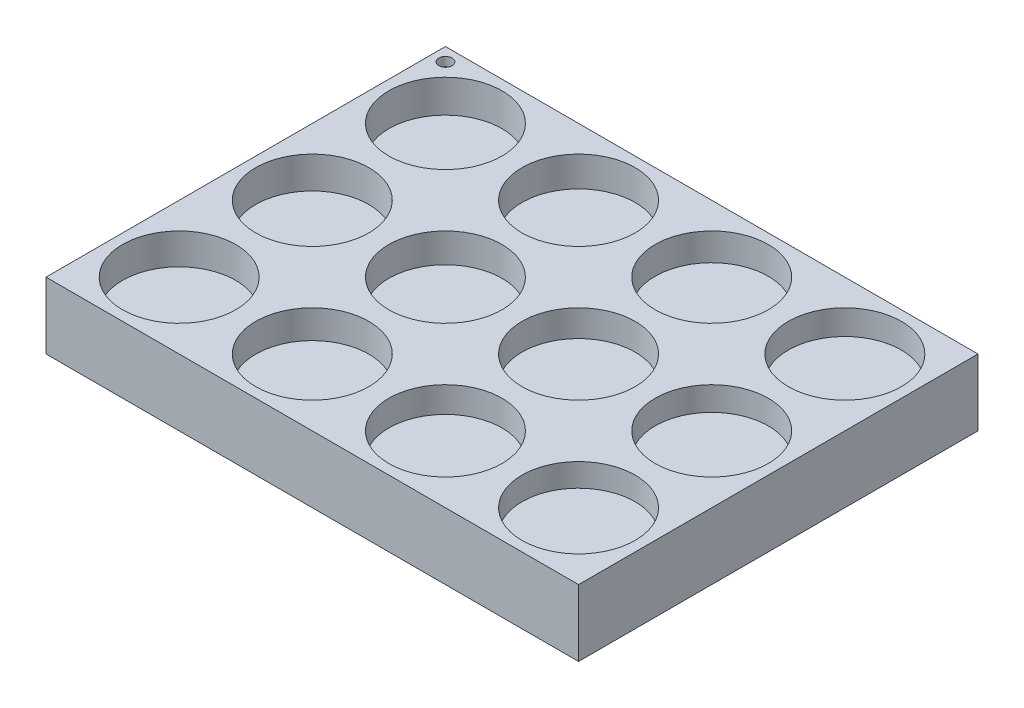
SolidWorks part; units mm, degrees
ref_plane "Front Plane" through (0, 0, 0) normal (0, 0, 1) x (1, 0, 0)
ref_plane "Top Plane" through (0, 0, 0) normal (0, 1, 0) x (1, 0, 0)
ref_plane "Right Plane" through (0, 0, 0) normal (1, 0, 0) x (0, 0, -1)
sketch "Sketch1" plane through (0, 0, 0) normal (0, 1, 0) x (1, 0, 0)
  line L0 (-45, 30) -> (45, 30) construction
  line L1 (60, -45) -> (-60, -45)
  line L2 (60, -45) -> (60, 45)
  line L3 (60, 45) -> (-60, 45)
  line L4 (-60, -45) -> (-60, 45)
  line L5 (60, -45) -> (-60, 45) construction
  line L6 (60, 45) -> (-60, -45) construction
  line L8 (-15, 45) -> (15, 45) construction
  line L9 (-15, 45) -> (-15, 0) construction
  line L10 (-15, 0) -> (15, 0) construction
  line L11 (15, 45) -> (15, 0) construction
  circle A0 centre (-45, 30) radius 5
  circle A1 centre (-15, 30) radius 5
  circle A2 centre (15, 30) radius 5
  circle A3 centre (45, 30) radius 5
  circle A4 centre (-45, 0) radius 5
  circle A5 centre (-15, 0) radius 5
  circle A6 centre (15, 0) radius 5
  circle A7 centre (45, 0) radius 5
  circle A8 centre (-45, -30) radius 5
  circle A9 centre (-15, -30) radius 5
  circle A10 centre (15, -30) radius 5
  circle A11 centre (45, -30) radius 5
  point P0 (0, 0)
  point P14 (0, 30)
  point P15 (0, 0)
  dimension "D3" = 10
  dimension "D1" = 120
  dimension "D2" = 90
  dimension "D4" = 15
  dimension "D5" = 15
  dimension "D6" = 30
  dimension "D8" = 30
  dimension "D7" = 3
extrude "Boss-Extrude1" add sketch "Sketch1" along normal blind 5
sketch "Sketch3" plane through (0, 5, 0) normal (0, 1, 0) x (1, 0, 0)
  line L1 (-60, 45) -> (60, 45)
  line L2 (-60, 45) -> (-60, -45)
  line L3 (-60, -45) -> (60, -45)
  line L4 (60, 45) -> (60, -45)
extrude "Boss-Extrude6" add sketch "Sketch3" along normal blind 10
sketch "Sketch2" plane through (0, 15, 0) normal (0, 1, 0) x (1, 0, 0)
  line L1 (-60, 45) -> (-30, 45) construction
  line L2 (-60, 45) -> (-60, 15) construction
  line L3 (-60, 15) -> (-30, 15) construction
  line L4 (-30, 45) -> (-30, 15) construction
  line L5 (-60, 15) -> (-30, 15) construction
  line L6 (-60, 15) -> (-60, -15) construction
  line L7 (-60, -15) -> (-30, -15) construction
  line L8 (-30, 15) -> (-30, -15) construction
  line L9 (-60, -15) -> (-30, -15) construction
  line L10 (-60, -15) -> (-60, -45) construction
  line L11 (-60, -45) -> (-30, -45) construction
  line L12 (-30, -15) -> (-30, -45) construction
  line L14 (-30, 45) -> (0, 45) construction
  line L15 (-30, 45) -> (-30, 15) construction
  line L16 (-30, 15) -> (0, 15) construction
  line L17 (0, 45) -> (0, 15) construction
  line L18 (-30, 15) -> (0, 15) construction
  line L19 (-30, 15) -> (-30, -15) construction
  line L20 (-30, -15) -> (0, -15) construction
  line L21 (0, 15) -> (0, -15) construction
  line L22 (-30, -15) -> (0, -15) construction
  line L23 (-30, -15) -> (-30, -45) construction
  line L24 (-30, -45) -> (0, -45) construction
  line L25 (0, -15) -> (0, -45) construction
  line L26 (0, 45) -> (30, 45) construction
  line L27 (0, 45) -> (0, 15) construction
  line L28 (0, 15) -> (30, 15) construction
  line L29 (30, 45) -> (30, 15) construction
  line L30 (0, 15) -> (30, 15) construction
  line L31 (0, 15) -> (0, -15) construction
  line L32 (0, -15) -> (30, -15) construction
  line L33 (30, 15) -> (30, -15) construction
  line L34 (0, -15) -> (30, -15) construction
  line L35 (0, -15) -> (0, -45) construction
  line L36 (0, -45) -> (30, -45) construction
  line L37 (30, -15) -> (30, -45) construction
  line L38 (30, 45) -> (60, 45) construction
  line L39 (30, 45) -> (30, 15) construction
  line L40 (30, 15) -> (60, 15) construction
  line L41 (60, 45) -> (60, 15) construction
  line L43 (30, 15) -> (60, 15) construction
  line L44 (30, 15) -> (30, -15) construction
  line L45 (30, -15) -> (60, -15) construction
  line L46 (60, 15) -> (60, -15) construction
  line L47 (30, -15) -> (60, -15) construction
  line L48 (30, -15) -> (30, -45) construction
  line L49 (30, -45) -> (60, -45) construction
  line L50 (60, -15) -> (60, -45) construction
  circle A0 centre (-45, 30) radius 12.75
  circle A1 centre (-15, 30) radius 12.75
  circle A2 centre (15, 30) radius 12.75
  circle A3 centre (45, 30) radius 12.75
  circle A4 centre (-45, 0) radius 12.75
  circle A5 centre (-15, 0) radius 12.75
  circle A6 centre (15, 0) radius 12.75
  circle A7 centre (45, 0) radius 12.75
  circle A8 centre (-45, -30) radius 12.75
  circle A9 centre (-15, -30) radius 12.75
  circle A10 centre (15, -30) radius 12.75
  circle A11 centre (45, -30) radius 12.75
  point P33 (-45, 45)
  point P35 (-60, 30)
  point P38 (-15, 15)
  point P40 (15, 15)
  point P42 (45, 15)
  dimension "D1" = 25.5
  dimension "D3" = 30
  dimension "D2" = 3
extrude "Cut-Extrude1" cut sketch "Sketch2" against normal offset from surface (7.4 mm away) 2.6 contours A0 region at (-45, 15, -30) up to face at (-45, 5, -25)
extrude "Cut-Extrude2" cut sketch "Sketch2<8>" against normal offset from surface (7.2 mm away) 2.8 contours A4 region at (-45, 15, 0) up to face at (-45, 5, 5)
sketch "Sketch2<8>" plane through (0, 15, 0) normal (0, 1, 0) x (1, 0, 0) same geometry as "Sketch2"
extrude "Cut-Extrude3" cut sketch "Sketch2<9>" against normal offset from surface (7 mm away) 3 contours A8 region at (-45, 15, 30) up to face at (-45, 5, 35)
sketch "Sketch2<9>" plane through (0, 15, 0) normal (0, 1, 0) x (1, 0, 0) same geometry as "Sketch2"
extrude "Cut-Extrude4" cut sketch "Sketch2<10>" against normal offset from surface (6.8 mm away) 3.2 contours A1 region at (-15, 15, -30) up to face at (-15, 5, -25)
sketch "Sketch2<10>" plane through (0, 15, 0) normal (0, 1, 0) x (1, 0, 0) same geometry as "Sketch2"
extrude "Cut-Extrude5" cut sketch "Sketch2<11>" against normal offset from surface (6.6 mm away) 3.4 contours A5 region at (-15, 15, 0) up to face at (-15, 5, 5)
sketch "Sketch2<11>" plane through (0, 15, 0) normal (0, 1, 0) x (1, 0, 0) same geometry as "Sketch2"
extrude "Cut-Extrude6" cut sketch "Sketch2<12>" against normal offset from surface (6.4 mm away) 3.6 contours A9 region at (-15, 15, 30) up to face at (-15, 5, 35)
sketch "Sketch2<12>" plane through (0, 15, 0) normal (0, 1, 0) x (1, 0, 0) same geometry as "Sketch2"
extrude "Cut-Extrude7" cut sketch "Sketch2<13>" against normal offset from surface (6.2 mm away) 3.8 contours A2 region at (15, 15, -30) up to face at (15, 5, -25)
sketch "Sketch2<13>" plane through (0, 15, 0) normal (0, 1, 0) x (1, 0, 0) same geometry as "Sketch2"
extrude "Cut-Extrude8" cut sketch "Sketch2<14>" against normal offset from surface (6 mm away) 4 contours A6 region at (15, 15, 0) up to face at (15, 5, 5)
sketch "Sketch2<14>" plane through (0, 15, 0) normal (0, 1, 0) x (1, 0, 0) same geometry as "Sketch2"
extrude "Cut-Extrude9" cut sketch "Sketch2<15>" against normal offset from surface (5.8 mm away) 4.2 contours A10 region at (15, 15, 30) up to face at (15, 5, 35)
sketch "Sketch2<15>" plane through (0, 15, 0) normal (0, 1, 0) x (1, 0, 0) same geometry as "Sketch2"
extrude "Cut-Extrude10" cut sketch "Sketch2<16>" against normal offset from surface (5.6 mm away) 4.4 contours A3 region at (45, 15, -30) up to face at (45, 5, -25)
sketch "Sketch2<16>" plane through (0, 15, 0) normal (0, 1, 0) x (1, 0, 0) same geometry as "Sketch2"
extrude "Cut-Extrude11" cut sketch "Sketch2<17>" against normal offset from surface (5.4 mm away) 4.6 contours A7 region at (45, 15, 0) up to face at (45, 5, 5)
sketch "Sketch2<17>" plane through (0, 15, 0) normal (0, 1, 0) x (1, 0, 0) same geometry as "Sketch2"
extrude "Cut-Extrude12" cut sketch "Sketch2<18>" against normal offset from surface (5.2 mm away) 4.8 contours A11 region at (45, 15, 30) up to face at (45, 5, 35)
sketch "Sketch2<18>" plane through (0, 15, 0) normal (0, 1, 0) x (1, 0, 0) same geometry as "Sketch2"
sketch "Sketch4" plane through (0, 15, 0) normal (0, 1, 0) x (1, 0, 0)
  line L0 (-60, 45) -> (-54.0156, 39.0156) construction
  line L1 (60, 45) -> (-60, 45) construction
  circle A0 centre (-57.0078, 42.0078) radius 1.5
  circle A1 centre (-45, 30) radius 12.75 construction
  point P9 (0, 0)
  point P10 (-57.0078, 42.0078)
  dimension "D2" = 3
  dimension "D1" = 45
extrude "Cut-Extrude13" cut sketch "Sketch4" against normal blind 2
